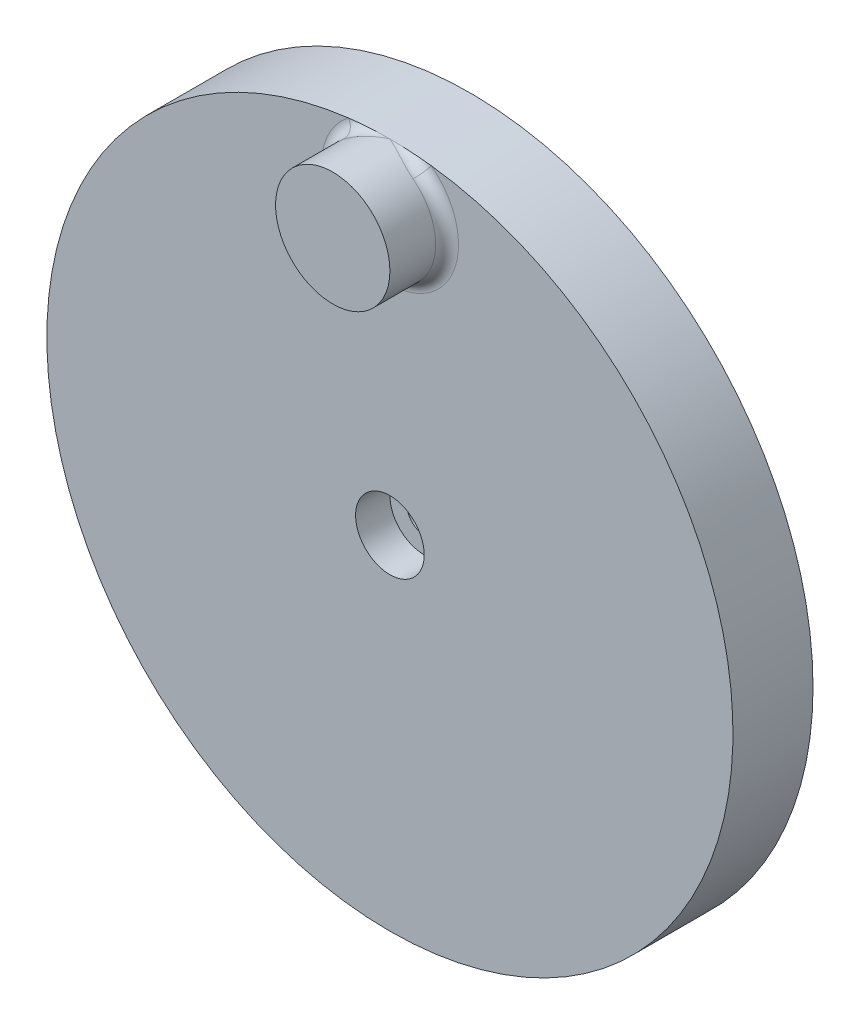
SolidWorks part; units mm, degrees
ref_plane "Front Plane" through (0, 0, 0) normal (0, 0, 1) x (1, 0, 0)
ref_plane "Top Plane" through (0, 0, 0) normal (0, 1, 0) x (1, 0, 0)
ref_plane "Right Plane" through (0, 0, 0) normal (1, 0, 0) x (0, 0, -1)
sketch "Sketch1" plane through (0, 0, 0) normal (0, 0, 1) x (1, 0, 0)
  line L0 (-2.4759, 16.8466) -> (-4.3, 3.8174)
  line L1 (2.4759, 16.8466) -> (4.3, 3.8174)
  line L2 (-4.3, -3.8174) -> (-2.4759, -16.8466)
  line L3 (4.3, -3.8174) -> (2.4759, -16.8466)
  arc A0 (4.3, 3.8174) -> (4.3, -3.8174) centre (0, 0) cw
  arc A1 (-4.3, 3.8174) -> (-4.3, -3.8174) centre (0, 0) ccw
  arc A2 (-2.4759, 16.8466) -> (2.4759, 16.8466) centre (0, 16.5) cw
  arc A3 (-2.4759, -16.8466) -> (2.4759, -16.8466) centre (0, -16.5) ccw
sketch "Sketch2" plane through (0, 0, 0) normal (0, 0, 1) x (1, 0, 0)
  circle A0 centre (0, 0) radius 30
  dimension "D1" = 60
extrude "Boss-Extrude1" add sketch "Sketch2" along normal blind 7
extrude "Cut-Extrude1" cut sketch "Sketch1" along normal blind 2
ref_plane "Plane1" through (0, 0, 0) normal (0, 0, -1) x (-1, 0, 0)
sketch "Sketch3" plane through (0, 0, 0) normal (0, 0, -1) x (-1, 0, 0)
  circle A0 centre (0, 0) radius 1.5
  dimension "D1" = 3
extrude "Cut-Extrude2" cut sketch "Sketch3" against normal through all both and the other way through all
ref_plane "Plane2" through (0, 0, 7) normal (0, 0, 1) x (1, 0, 0)
sketch "Sketch4" plane through (0, 0, 7) normal (0, 0, 1) x (1, 0, 0)
  circle A0 centre (0, 0) radius 3
extrude "Cut-Extrude3" cut sketch "Sketch4" against normal blind 3
sketch "Sketch5" plane through (0, 0, 7) normal (0, 0, 1) x (1, 0, 0)
  line L0 (0, 0) -> (0, 32.3355) construction
  circle A0 centre (0, 25) radius 5
  dimension "D2" = 10
  dimension "D1" = 25
extrude "Boss-Extrude2" add sketch "Sketch5" along normal blind 5
fillet "Fillet1" radius 1 1 edges at (5, 25, 7)
